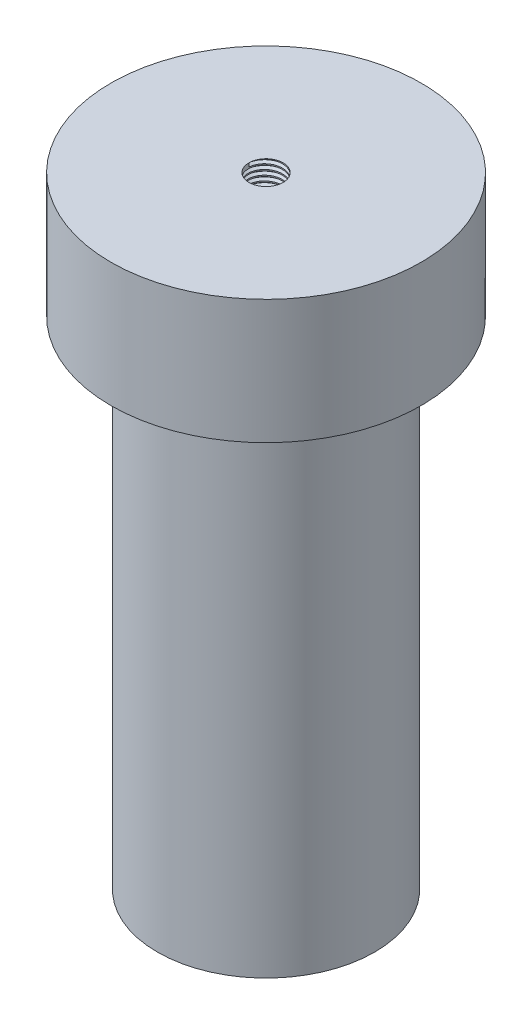
SolidWorks part; units mm, degrees
ref_plane "Front Plane" through (0, 0, 0) normal (0, 0, 1) x (1, 0, 0)
ref_plane "Top Plane" through (0, 0, 0) normal (0, 1, 0) x (1, 0, 0)
ref_plane "Right Plane" through (0, 0, 0) normal (1, 0, 0) x (0, 0, -1)
sketch "Sketch1" plane through (0, 0, 0) normal (0, 1, 0) x (1, 0, 0)
  circle A0 centre (0, 0) radius 17.5
  dimension "D1" = 35
extrude "Boss-Extrude1" add sketch "Sketch1" against normal blind 100
sketch "Sketch2" plane through (0, 0, 0) normal (0, 1, 0) x (1, 0, 0)
  circle A0 centre (0, 0) radius 25
  dimension "D1" = 50
extrude "Boss-Extrude2" add sketch "Sketch2" against normal blind 20
sketch "Sketch3" plane through (0, 0, 0) normal (0, 1, 0) x (1, 0, 0)
  circle A0 centre (0, 0) radius 2.75
  dimension "D1" = 5.5
extrude "Cut-Extrude1" cut sketch "Sketch3" against normal blind 10
thread "Thread1" pitch 0.8 method cut profile "Thread Profile1" start angle 0, offset 0, length 10, pitch 0.8, diameter 5.5
ref_plane "Plane1" through (-2.75, 0, 0) normal (0, 0, 1) x (-1, 0, 0)
sketch "Thread Profile1" plane through (-2.75, 0, 0) normal (0, 0, 1) x (-1, 0, 0)
  line L0 (0, 0) -> (0, 0.8) construction
  line L1 (0, 0) -> (0.433, 0.25)
  line L2 (0.433, 0.25) -> (0.433, 0.35)
  line L3 (0.433, 0.35) -> (0, 0.6)
  line L4 (0.433, 0.3) -> (0, 0.3) construction
  line L11 (0, 0) -> (0, 0.6)
  point P2 (0, 0)
  dimension "Pitch" = 0.8
  dimension "Profile_Angle" = 60
  dimension "Profile_Land" = 0.1
  dimension "Profile_Height" = 0.433
